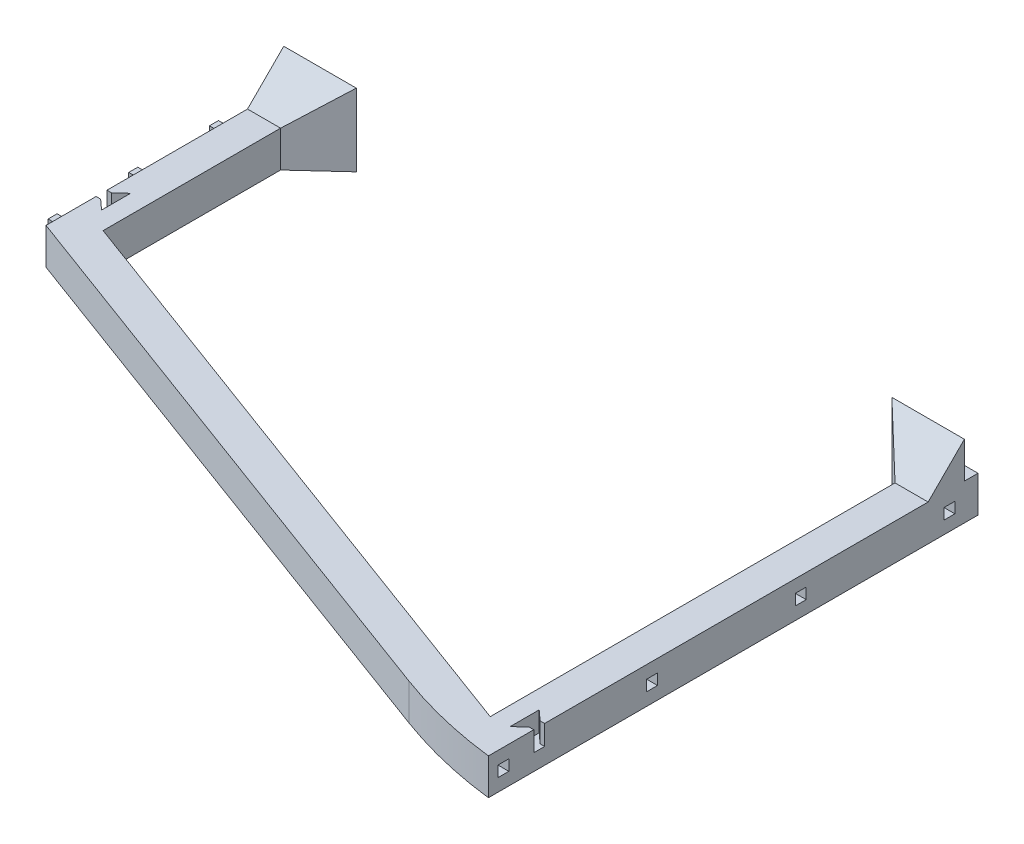
SolidWorks part; units mm, degrees
ref_plane "Přední rovina" through (0, 0, 0) normal (0, 0, 1) x (1, 0, 0)
ref_plane "Horní rovina" through (0, 0, 0) normal (0, 1, 0) x (1, 0, 0)
ref_plane "Pravá rovina" through (0, 0, 0) normal (1, 0, 0) x (0, 0, -1)
sketch "Skica1" plane through (0, 0, 0) normal (0, 1, 0) x (1, 0, 0)
  line L0 (0, 0) -> (0, -111)
  line L1 (0, -111) -> (-150.15, -55.45)
  line L2 (-150.15, -55.45) -> (-150.15, 0)
  line L3 (-150.15, 0) -> (-142.85, 0)
  line L4 (-142.85, 0) -> (-142.85, -50.1539)
  line L5 (-142.85, -50.1539) -> (-7.3, -100.3024)
  line L6 (-7.3, -100.3024) -> (-7.3, 0)
  line L7 (-7.3, 0) -> (0, 0)
  dimension "D1" = 111
  dimension "D2" = 7.3
  dimension "D3" = 7.3
  dimension "D4" = 150.15
  dimension "D5" = 7.5
  dimension "D6" = 55.45
extrude "Přidat vysunutím1" add sketch "Skica1" along normal blind 8
sketch "Skica3" plane through (0, 8, 0) normal (0, 1, 0) x (1, 0, 0)
  line L12 (0, -111) -> (0, 0) construction
  line L13 (-3.2, -93.6) -> (0, -93.6)
  line L14 (-3.2, -93.6) -> (-3.2, -100)
  line L15 (-3.2, -100) -> (0, -100)
  line L16 (0, -93.6) -> (0, -100)
  line L17 (0, -95.6) -> (-1, -95.6)
  line L18 (-1, -95.6) -> (-3.2, -93.6)
  line L19 (-3.2, -100) -> (-1, -98)
  line L20 (-1, -98) -> (0, -98)
  line L21 (0, -98) -> (0, -95.6)
  dimension "D1" = 6.4
  dimension "D2" = 3.2
  dimension "D3" = 2.4
  dimension "D4" = 2
  dimension "D5" = 1
  dimension "D6" = 1
  dimension "D7" = 11
extrude "Odebrat vysunutím1" cut sketch "Skica3" against normal blind 4.4 contours L19 L20 L16 L17 L18 L14 region at (-1.9157, 8, 96.8)
sketch "Skica6" plane through (0, 8, 0) normal (0, 1, 0) x (1, 0, 0)
  line L0 (-150.15, 0) -> (-150.15, -55.45) construction
  line L9 (-150.15, -3) -> (-134.15, -3)
  line L10 (-150.15, -3) -> (-150.15, -11)
  line L11 (-150.15, -11) -> (-134.15, -11)
  line L12 (-134.15, -3) -> (-134.15, -11)
  line L13 (-142.85, 0) -> (-150.15, 0) construction
  line L14 (0, -95.6) -> (0, 0) construction
  line L15 (0, -3) -> (-16, -3)
  line L16 (0, -3) -> (0, -11)
  line L17 (0, -11) -> (-16, -11)
  line L18 (-16, -3) -> (-16, -11)
  line L19 (0, 0) -> (-7.3, 0) construction
  dimension "D1" = 3
  dimension "D2" = 16
  dimension "D3" = 3
  dimension "D4" = 8
  dimension "D5" = 16
  dimension "D6" = 8
extrude "Přidat vysunutím3" add sketch "Skica6" against normal blind 16 from offset 8 contours L15 L18 L17 L16 | L9 L12 L11 L10
sketch "Skica8" plane through (0, 0, 0) normal (1, 0, 0) x (0, 0, -1)
  line L3 (-11, 8) -> (-11, 16)
  line L4 (-11, 16) -> (-3, 16)
  line L5 (-3, 16) -> (-11, 8)
extrude "Odebrat vysunutím3" cut sketch "Skica8" against normal through all
sketch "Skica9" plane through (0, 0, 0) normal (0, -1, 0) x (1, 0, 0)
  line L8 (-142.85, 11) -> (-134.15, 11)
  line L9 (-134.15, 11) -> (-134.15, 3)
  line L10 (-134.15, 3) -> (-142.85, 11)
  line L11 (-16, 11) -> (-7.3, 11)
  line L12 (-7.3, 11) -> (-16, 3)
  line L13 (-16, 3) -> (-16, 11)
extrude "Odebrat vysunutím4" cut sketch "Skica9" against normal through all
sketch "Skica4" plane through (0, 0, 0) normal (1, 0, 0) x (0, 0, -1)
  line L0 (-111, 8) -> (-98, 8) construction
  line L1 (-105.9, 5.2) -> (-103.5, 5.2)
  line L2 (-105.9, 5.2) -> (-105.9, 2.8)
  line L3 (-105.9, 2.8) -> (-103.5, 2.8)
  line L4 (-103.5, 5.2) -> (-103.5, 2.8)
  line L22 (-73.1, 5.2) -> (-70.7, 5.2)
  line L23 (-73.1, 5.2) -> (-73.1, 2.8)
  line L24 (-73.1, 2.8) -> (-70.7, 2.8)
  line L25 (-70.7, 5.2) -> (-70.7, 2.8)
  line L26 (-40.3, 5.2) -> (-37.9, 5.2)
  line L27 (-40.3, 5.2) -> (-40.3, 2.8)
  line L28 (-40.3, 2.8) -> (-37.9, 2.8)
  line L29 (-37.9, 5.2) -> (-37.9, 2.8)
  line L30 (-7.5, 5.2) -> (-5.1, 5.2)
  line L31 (-7.5, 5.2) -> (-7.5, 2.8)
  line L32 (-7.5, 2.8) -> (-5.1, 2.8)
  line L33 (-5.1, 5.2) -> (-5.1, 2.8)
  line L34 (-3, 8) -> (0, 8) construction
  line L35 (-111, 0) -> (0, 0) construction
  line L37 (0, 8) -> (0, 0) construction
  point P18 (-6.3, 2.8)
  dimension "D1" = 2.4
  dimension "D2" = 2.4
  dimension "D3" = 2.8
  dimension "D4" = 5.1
  dimension "D5" = 2.4
  dimension "D6" = 2.4
  dimension "D7" = 2.8
  dimension "D8" = 30.4
  dimension "D9" = 30.4
  dimension "D10" = 2.4
  dimension "D11" = 2.4
  dimension "D12" = 2.8
  dimension "D13" = 2.8
  dimension "D14" = 2.4
  dimension "D15" = 2.4
  dimension "D16" = 30.4
extrude "Odebrat vysunutím2" cut sketch "Skica4" against normal blind 4.4
sketch "Skica5" plane through (-150.15, 0, 0) normal (-1, 0, 0) x (0, 0, 1)
  line L0 (0, 8) -> (3, 8) construction
  line L1 (13.4, 5) -> (15.4, 5)
  line L2 (13.4, 5) -> (13.4, 3)
  line L3 (13.4, 3) -> (15.4, 3)
  line L4 (15.4, 5) -> (15.4, 3)
  line L5 (31.2, 5) -> (33.2, 5)
  line L6 (31.2, 5) -> (31.2, 3)
  line L7 (31.2, 3) -> (33.2, 3)
  line L8 (33.2, 5) -> (33.2, 3)
  line L9 (0, 8) -> (0, 0) construction
  line L11 (49, 5) -> (51, 5)
  line L12 (49, 5) -> (49, 3)
  line L13 (49, 3) -> (51, 3)
  line L14 (51, 5) -> (51, 3)
  dimension "D1" = 2
  dimension "D2" = 2
  dimension "D3" = 3
  dimension "D4" = 13.4
  dimension "D5" = 15.8
  dimension "D6" = 2
  dimension "D7" = 2
  dimension "D8" = 3
  dimension "D9" = 15.8
  dimension "D10" = 2
  dimension "D11" = 2
  dimension "D12" = 3
extrude "Přidat vysunutím2" add sketch "Skica5" along normal blind 4
sketch "Skica10" plane through (0, 8, 0) normal (0, 1, 0) x (1, 0, 0)
  line L0 (-150.15, -44.4) -> (-149.15, -44.4)
  line L5 (-142.85, 0) -> (-150.15, 0) construction
  line L6 (-150.15, -11) -> (-150.15, -55.45) construction
  line L7 (-150.15, -42) -> (-149.15, -42)
  line L8 (-149.15, -42) -> (-146.95, -40)
  line L9 (-146.95, -40) -> (-146.95, -46.4)
  line L10 (-146.95, -46.4) -> (-149.15, -44.4)
  line L11 (-150.15, -44.4) -> (-150.15, -42)
  dimension "D1" = 6.4
  dimension "D2" = 2.4
  dimension "D3" = 1
  dimension "D4" = 1
  dimension "D5" = 2
  dimension "D6" = 3.2
  dimension "D7" = 40
extrude "Odebrat vysunutím5" cut sketch "Skica10" against normal blind 4.4
sketch "Skica11" plane through (0, 8, 0) normal (0, 1, 0) x (1, 0, 0)
  line L0 (0, -108) -> (-8.1089, -108)
  line L1 (0, -111) -> (0, -98) construction
  line L2 (-150.15, -55.45) -> (0, -111) construction
  line L3 (-8.1089, -108) -> (0, -111)
  line L4 (0, -111) -> (0, -108)
  dimension "D1" = 3
extrude "Odebrat vysunutím6" cut sketch "Skica11" against normal through all
fillet "Zaoblit1" radius 100 1 edges at (-8.1089, 4, 108)
